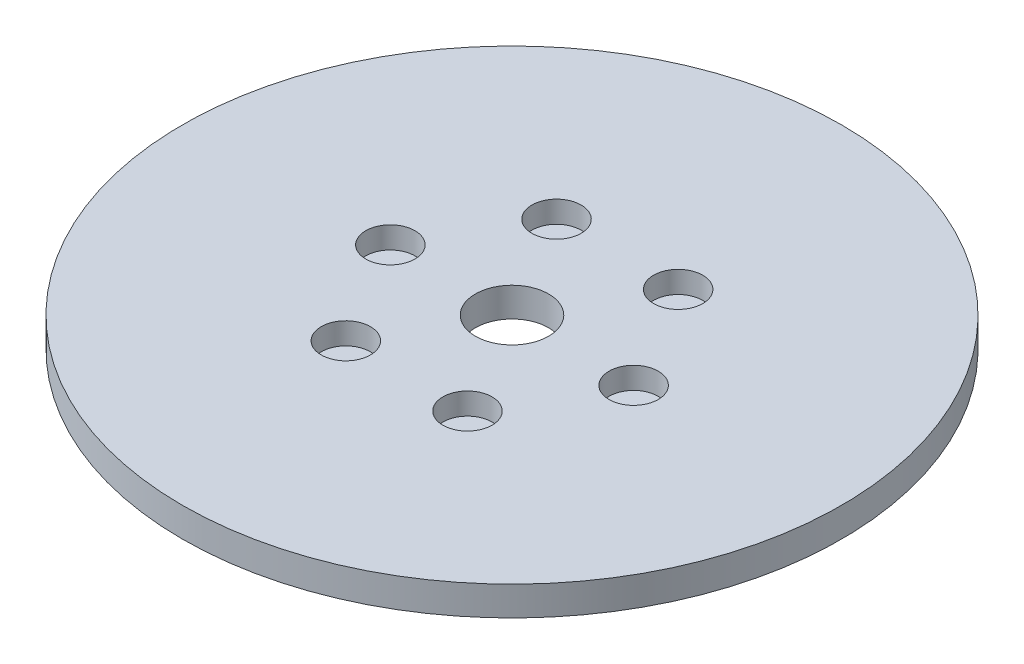
SolidWorks part; units mm, degrees
ref_plane "Front Plane" through (0, 0, 0) normal (0, 0, 1) x (1, 0, 0)
ref_plane "Top Plane" through (0, 0, 0) normal (0, 1, 0) x (1, 0, 0)
ref_plane "Right Plane" through (0, 0, 0) normal (1, 0, 0) x (0, 0, -1)
sketch "Sketch1" plane through (0, 0, 0) normal (0, 1, 0) x (1, 0, 0)
  circle A0 centre (0, 0) radius 90
  dimension "FLANGE_OD" = 180
extrude "Boss-Extrude1" add sketch "Sketch1" along normal blind 8
sketch "Sketch2" plane through (0, 0, 0) normal (0, 1, 0) x (1, 0, 0)
  circle A0 centre (0, 0) radius 10
  dimension "BORE_D" = 20
extrude "Cut-Extrude1" cut sketch "Sketch2" along normal through all
sketch "Sketch3" plane through (0, 8, 0) normal (0, 1, 0) x (1, 0, 0)
  circle A0 centre (0, 0) radius 33.2178 construction
  circle A1 centre (-33.2178, 0) radius 6.7143
  dimension "BOLT_D" = 13.4285
  dimension "BOLT_PCD" = 66.4356
extrude "Cut-Extrude2" cut sketch "Sketch3" against normal blind 5.9572
pattern_circular "CirPattern1" count 6 over 360 about axis through (0, 0, 0) along (0, 1, 0) of "Cut-Extrude2"
